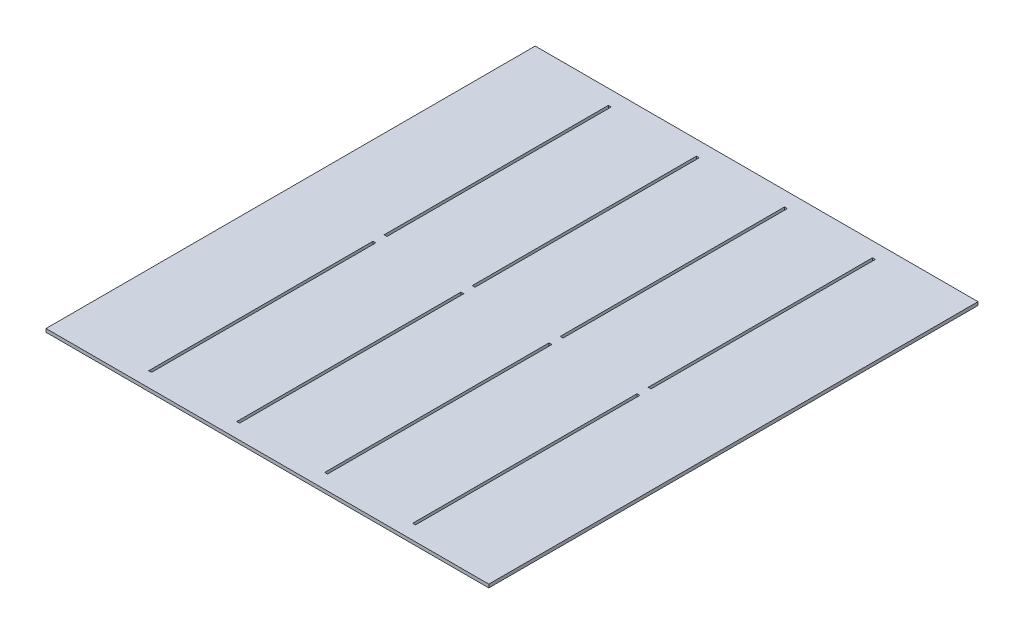
SolidWorks part; units mm, degrees
material "6063-T6"
ref_plane "Front Plane" through (0, 0, 0) normal (0, 0, 1) x (1, 0, 0)
ref_plane "Top Plane" through (0, 0, 0) normal (0, 1, 0) x (1, 0, 0)
ref_plane "Right Plane" through (0, 0, 0) normal (1, 0, 0) x (0, 0, -1)
sketch "Sketch1" plane through (0, 0, 0) normal (0, 1, 0) x (1, 0, 0)
  line L0 (87.74, 480.4) -> (87.74, 0) construction
  line L1 (0, 0) -> (434.8, 0)
  line L2 (0, 0) -> (0, 480.4)
  line L3 (0, 480.4) -> (434.8, 480.4)
  line L4 (434.8, 0) -> (434.8, 480.4)
  line L5 (174.18, 480.4) -> (174.18, 0) construction
  line L6 (260.62, 480.4) -> (260.62, 0) construction
  line L7 (87.74, 302.5963) -> (174.18, 302.5963) construction
  line L8 (174.18, 263.4867) -> (260.62, 263.4867) construction
  line L9 (347.06, 480.4) -> (347.06, 0) construction
  line L10 (260.62, 215.6774) -> (347.06, 215.6774) construction
  line L11 (0, 145.8088) -> (87.74, 145.8088) construction
  line L12 (347.06, 135.9861) -> (434.8, 135.9861) construction
  line L13 (0, 477.8112) -> (434.8, 477.8112) construction
  line L14 (434.8, 2.5888) -> (0, 2.5888) construction
  line L15 (86.3456, 480.4) -> (86.3456, 0) construction
  line L16 (172.7856, 480.4) -> (172.7856, 0) construction
  line L17 (259.2256, 480.4) -> (259.2256, 0) construction
  line L18 (345.6656, 480.4) -> (345.6656, 0) construction
  line L19 (89.1344, 480.4) -> (89.1344, 0) construction
  line L20 (175.5744, 480.4) -> (175.5744, 0) construction
  line L21 (262.0144, 480.4) -> (262.0144, 0) construction
  line L22 (348.4544, 480.4) -> (348.4544, 0) construction
  line L23 (87.74, 480.4) -> (87.74, 465.9112) construction
  line L24 (86.3456, 465.9112) -> (89.1344, 465.9112)
  line L25 (86.3456, 465.9112) -> (86.3456, 245.7112)
  line L26 (86.3456, 245.7112) -> (89.1344, 245.7112)
  line L27 (89.1344, 465.9112) -> (89.1344, 245.7112)
  line L28 (86.3456, 234.6888) -> (89.1344, 234.6888)
  line L29 (86.3456, 234.6888) -> (86.3456, 14.4888)
  line L30 (86.3456, 14.4888) -> (89.1344, 14.4888)
  line L31 (89.1344, 234.6888) -> (89.1344, 14.4888)
  line L32 (87.74, 14.4888) -> (87.74, 0) construction
  line L33 (172.7856, 465.9112) -> (175.5744, 465.9112)
  line L34 (175.5744, 465.9112) -> (175.5744, 245.7112)
  line L35 (172.7856, 465.9112) -> (172.7856, 245.7112)
  line L36 (172.7856, 245.7112) -> (175.5744, 245.7112)
  line L37 (172.7856, 234.6888) -> (175.5744, 234.6888)
  line L38 (175.5744, 234.6888) -> (175.5744, 14.4888)
  line L39 (172.7856, 234.6888) -> (172.7856, 14.4888)
  line L40 (172.7856, 14.4888) -> (175.5744, 14.4888)
  line L41 (259.2256, 465.9112) -> (262.0144, 465.9112)
  line L42 (262.0144, 465.9112) -> (262.0144, 245.7112)
  line L43 (259.2256, 465.9112) -> (259.2256, 245.7112)
  line L44 (259.2256, 245.7112) -> (262.0144, 245.7112)
  line L45 (259.2256, 234.6888) -> (262.0144, 234.6888)
  line L46 (262.0144, 234.6888) -> (262.0144, 14.4888)
  line L47 (259.2256, 234.6888) -> (259.2256, 14.4888)
  line L48 (259.2256, 14.4888) -> (262.0144, 14.4888)
  line L49 (345.6656, 465.9112) -> (348.4544, 465.9112)
  line L50 (348.4544, 465.9112) -> (348.4544, 245.7112)
  line L51 (345.6656, 465.9112) -> (345.6656, 245.7112)
  line L52 (345.6656, 245.7112) -> (348.4544, 245.7112)
  line L53 (345.6656, 234.6888) -> (348.4544, 234.6888)
  line L54 (348.4544, 234.6888) -> (348.4544, 14.4888)
  line L55 (345.6656, 234.6888) -> (345.6656, 14.4888)
  line L56 (345.6656, 14.4888) -> (348.4544, 14.4888)
  dimension "D1" = 480.4
  dimension "D2" = 434.8
  dimension "D3" = 86.44
  dimension "D4" = 2.5888
  dimension "D5" = 2.5888
  dimension "D8" = 220.2
  dimension "D9" = 11.9
  dimension "D10" = 11.9
  dimension "D11" = 4
  dimension "D12" = 86.44
  dimension "D13" = 11.0224
  dimension "D6" = 1.3944
  dimension "D7" = 1.3944
base flange "Base-Flange2" sketch "Sketch1" thickness 3.264 reverse thickness direction no parameters "D1"=3
sketch "Bend-Lines3" [suppressed] plane through (0, 0, 0) normal (0, 1, 0) x (1, 0, 0)
sketch "Bounding-Box3" [suppressed] plane through (0, 0, 0) normal (0, 1, 0) x (1, 0, 0)
sheet metal parameters "Sheet-Metal2" thickness 3.264 parameters "D1"=3
flat pattern "Flat-Pattern2" [suppressed]
sketch "Bend-Lines4" plane through (0, 0, 0) normal (0, 1, 0) x (1, 0, 0)
sketch3d "Bounding-Box4" [suppressed]
  line L0 (0, 0, 0) -> (0, 480.4, 0) construction
  line L1 (434.8, 0, 0) -> (434.8, 480.4, 0) construction
  line L2 (0, 0, 0) -> (434.8, 0, 0) construction
  line L3 (0, 480.4, 0) -> (434.8, 480.4, 0) construction
